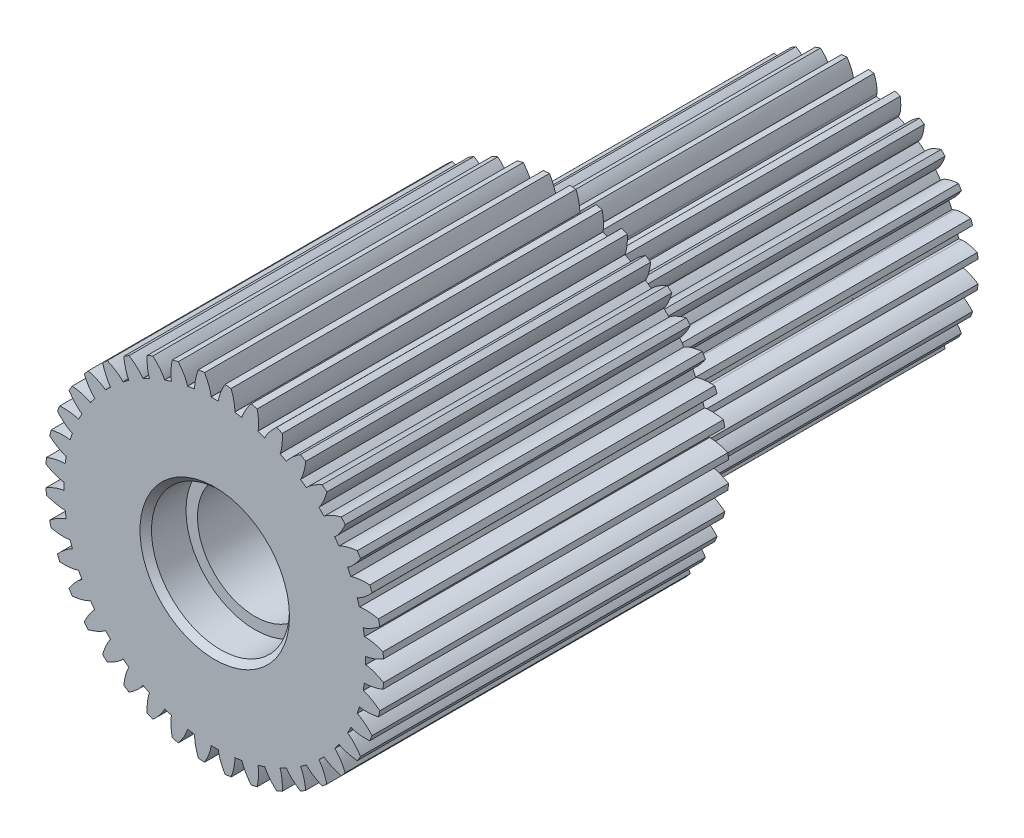
SolidWorks part; units mm, degrees
material "PLA"
ref_plane "Front Plane" through (0, 0, 0) normal (0, 0, 1) x (1, 0, 0)
ref_plane "Top Plane" through (0, 0, 0) normal (0, 1, 0) x (1, 0, 0)
ref_plane "Right Plane" through (0, 0, 0) normal (1, 0, 0) x (0, 0, -1)
sketch "Sketch1" plane through (0, 0, 0) normal (0, 0, 1) x (1, 0, 0)
  circle A0 centre (0, 0) radius 14.7
  dimension "D1" = 29.4
extrude "Boss-Extrude1" add sketch "Sketch1" along normal mid plane 29.9958
sketch "Sketch2" plane through (0, 0, 0) normal (0, 0, 1) x (1, 0, 0)
  line L0 (0, 0) -> (13.9958, 0.3411) construction
  line L1 (0, 0) -> (14, 0) construction
  line L2 (0, 0) -> (13.9958, -0.3411) construction
  line L3 (13.1493, -0.3205) -> (13.1211, -0.3198)
  line L4 (13.1518, 0.3205) -> (13.1211, 0.3198)
  circle A0 centre (0, 0) radius 14 construction
  circle A1 centre (0, 0) radius 13.1557 construction
  circle A2 centre (0, 0) radius 13.125
  circle A3 centre (0, 0) radius 14.7 construction
  circle A4 centre (0, 0) radius 14.7
  spline S0 degree 4 poles (13.1518, 0.3205) (13.1563, 0.3207) (13.1689, 0.3214) (13.1927, 0.3235) (13.2314, 0.328) (13.2806, 0.3354) (13.344, 0.3469) (13.4184, 0.3629) (13.4998, 0.3829) (13.5879, 0.4075) (13.6755, 0.4343) (13.7623, 0.4634) (13.8485, 0.4943) (13.9523, 0.5341) (14.0761, 0.5851) (14.2195, 0.6494) (14.3807, 0.7279) (14.5433, 0.8137) (14.7019, 0.9031) (14.8603, 0.9988) (15.0122, 1.0952) (15.1681, 1.201) (15.3109, 1.3014) (15.4686, 1.4199) (15.5951, 1.5173) (15.7594, 1.6522) (15.8557, 1.7337) (15.9673, 1.8313) (16.0164, 1.8758) (16.0466, 1.9031) knots 0 0 0 0 0 0.005377 0.015084 0.028532 0.04661 0.064855 0.092111 0.119476 0.146842 0.174209 0.201575 0.228941 0.256307 0.307035 0.361767 0.4165 0.471232 0.525964 0.580697 0.635429 0.690161 0.744894 0.799626 0.854358 0.909091 0.954545 1 1 1 1 1 construction
  spline S1 degree 4 poles (13.1518, 0.3205) (13.1563, 0.3207) (13.1689, 0.3214) (13.1927, 0.3235) (13.2314, 0.328) (13.2806, 0.3354) (13.344, 0.3469) (13.4184, 0.3629) (13.4998, 0.3829) (13.5879, 0.4075) (13.6755, 0.4343) (13.7623, 0.4634) (13.8485, 0.4943) (13.9523, 0.5341) (14.0761, 0.5851) (14.2195, 0.6494) (14.3807, 0.7279) (14.5433, 0.8137) (14.7019, 0.9031) (14.8603, 0.9988) (15.0122, 1.0952) (15.1681, 1.201) (15.3109, 1.3014) (15.4686, 1.4199) (15.5951, 1.5173) (15.7238, 1.6229) (15.7861, 1.6751) (15.8178, 1.702) knots 0 0 0 0 0 0.005377 0.015084 0.028532 0.04661 0.064855 0.092111 0.119476 0.146842 0.174209 0.201575 0.228941 0.256307 0.307035 0.361767 0.4165 0.471232 0.525964 0.580697 0.635429 0.690161 0.744894 0.799626 0.854358 0.909091 0.909091 0.909091 0.909091 0.909091
  spline S2 degree 4 poles (13.1493, -0.3205) (13.1538, -0.3206) (13.1664, -0.3213) (13.1902, -0.3234) (13.2289, -0.3279) (13.2781, -0.3354) (13.3415, -0.3469) (13.4159, -0.3628) (13.4973, -0.3829) (13.5855, -0.4074) (13.673, -0.4343) (13.7599, -0.4633) (13.846, -0.4942) (13.9498, -0.534) (14.0736, -0.585) (14.2171, -0.6493) (14.3783, -0.7278) (14.5409, -0.8137) (14.6994, -0.903) (14.8578, -0.9987) (15.0098, -1.0952) (15.1656, -1.2009) (15.3085, -1.3013) (15.4661, -1.4198) (15.5927, -1.5173) (15.757, -1.6521) (15.8532, -1.7337) (15.9649, -1.8312) (16.0139, -1.8757) (16.0442, -1.9031) knots 0 0 0 0 0 0.005377 0.015084 0.028532 0.04661 0.064855 0.092111 0.119476 0.146842 0.174209 0.201575 0.228941 0.256307 0.307035 0.361767 0.4165 0.471232 0.525964 0.580697 0.635429 0.690161 0.744894 0.799626 0.854358 0.909091 0.954545 1 1 1 1 1 construction
  spline S3 degree 4 poles (13.1493, -0.3205) (13.1538, -0.3206) (13.1664, -0.3213) (13.1902, -0.3234) (13.2289, -0.3279) (13.2781, -0.3354) (13.3415, -0.3469) (13.4159, -0.3628) (13.4973, -0.3829) (13.5855, -0.4074) (13.673, -0.4343) (13.7599, -0.4633) (13.846, -0.4942) (13.9498, -0.534) (14.0736, -0.585) (14.2171, -0.6493) (14.3783, -0.7278) (14.5409, -0.8137) (14.6994, -0.903) (14.8578, -0.9987) (15.0098, -1.0952) (15.1656, -1.2009) (15.3085, -1.3013) (15.4661, -1.4198) (15.5927, -1.5173) (15.7214, -1.6229) (15.7837, -1.675) (15.8154, -1.702) knots 0 0 0 0 0 0.005377 0.015084 0.028532 0.04661 0.064855 0.092111 0.119476 0.146842 0.174209 0.201575 0.228941 0.256307 0.307035 0.361767 0.4165 0.471232 0.525964 0.580697 0.635429 0.690161 0.744894 0.799626 0.854358 0.909091 0.909091 0.909091 0.909091 0.909091
  dimension "D1" = 28
  dimension "D2" = 26.3114
  dimension "D3" = 26.25
  dimension "D4" = 1.396
  dimension "D5" = 1.396
extrude "Cut-Extrude1" cut sketch "Sketch2" against normal through all both and the other way through all contours A2 A4 region at (14.0491, -0.0005, 0)
pattern_circular "CirPattern2" count 40 over 360 about axis through (0, 0, 14.9979) along (0, 0, -1) of "Cut-Extrude1"
sketch "Sketch3" plane through (0, 0, 14.9979) normal (0, 0, 1) x (1, 0, 0)
  circle A0 centre (0, 0) radius 5
  dimension "D1" = 10
sketch "Sketch4" plane through (0, 0, -14.9979) normal (0, 0, -1) x (-1, 0, 0)
  circle A0 centre (0, 0) radius 10.5
  dimension "D1" = 21
extrude "Boss-Extrude2" add sketch "Sketch4" along normal blind 25.9129
sketch "Sketch5" plane through (0, 0, -40.9108) normal (0, 0, -1) x (-1, 0, 0)
  line L0 (0, 0) -> (10.5, 0) construction
  line L1 (0, 0) -> (10.4911, 0.4324) construction
  line L2 (0, 0) -> (10.4911, -0.4324) construction
  line L3 (9.1796, 0.3784) -> (8.9174, 0.3676)
  line L4 (9.1796, -0.3784) -> (8.9174, -0.3676)
  circle A0 centre (0, 0) radius 9.209 construction
  circle A1 centre (0, 0) radius 8.925
  arc A2 (10.4584, -0.9339) -> (10.4584, 0.9339) centre (0, 0) ccw
  spline S0 degree 4 poles (9.1796, 0.3784) (9.1827, 0.3785) (9.1915, 0.3792) (9.2082, 0.3809) (9.2352, 0.3846) (9.2853, 0.393) (9.3451, 0.4059) (9.4122, 0.4231) (9.4838, 0.4444) (9.5448, 0.4642) (9.6052, 0.4855) (9.6651, 0.5082) (9.7373, 0.5373) (9.8234, 0.5744) (9.923, 0.6211) (10.0349, 0.678) (10.1477, 0.74) (10.2576, 0.8044) (10.3674, 0.8732) (10.4726, 0.9425) (10.5804, 1.0183) (10.6792, 1.0903) (10.7882, 1.1751) (10.8756, 1.2448) (10.989, 1.3411) (11.0554, 1.3993) (11.1324, 1.4689) (11.1662, 1.5006) (11.187, 1.5201) knots 0 0 0 0 0 0.005377 0.015084 0.028532 0.04661 0.092111 0.119476 0.146842 0.174209 0.201575 0.228941 0.256307 0.307035 0.361767 0.4165 0.471232 0.525964 0.580697 0.635429 0.690161 0.744894 0.799626 0.854358 0.909091 0.954545 1 1 1 1 1 construction
  spline S1 degree 4 poles (9.1796, 0.3784) (9.1827, 0.3785) (9.1915, 0.3792) (9.2082, 0.3809) (9.2352, 0.3846) (9.2853, 0.393) (9.3451, 0.4059) (9.4122, 0.4231) (9.4838, 0.4444) (9.5448, 0.4642) (9.6052, 0.4855) (9.6651, 0.5082) (9.7373, 0.5373) (9.8234, 0.5744) (9.923, 0.6211) (10.0349, 0.678) (10.1477, 0.74) (10.2576, 0.8044) (10.3674, 0.8732) (10.4726, 0.9425) (10.5804, 1.0183) (10.6792, 1.0903) (10.7882, 1.1751) (10.8756, 1.2448) (10.9644, 1.3202) (11.0074, 1.3575) (11.0293, 1.3767) knots 0 0 0 0 0 0.005377 0.015084 0.028532 0.04661 0.092111 0.119476 0.146842 0.174209 0.201575 0.228941 0.256307 0.307035 0.361767 0.4165 0.471232 0.525964 0.580697 0.635429 0.690161 0.744894 0.799626 0.854358 0.909091 0.909091 0.909091 0.909091 0.909091
  spline S2 degree 4 poles (9.1796, -0.3784) (9.1827, -0.3785) (9.1915, -0.3792) (9.2082, -0.3809) (9.2352, -0.3846) (9.2853, -0.393) (9.3451, -0.4059) (9.4122, -0.4231) (9.4838, -0.4444) (9.5448, -0.4642) (9.6052, -0.4855) (9.6651, -0.5082) (9.7373, -0.5373) (9.8234, -0.5744) (9.923, -0.6211) (10.0349, -0.678) (10.1477, -0.74) (10.2576, -0.8044) (10.3674, -0.8732) (10.4726, -0.9425) (10.5804, -1.0183) (10.6792, -1.0903) (10.7882, -1.1751) (10.8756, -1.2448) (10.989, -1.3411) (11.0554, -1.3993) (11.1324, -1.4689) (11.1662, -1.5006) (11.187, -1.5201) knots 0 0 0 0 0 0.005377 0.015084 0.028532 0.04661 0.092111 0.119476 0.146842 0.174209 0.201575 0.228941 0.256307 0.307035 0.361767 0.4165 0.471232 0.525964 0.580697 0.635429 0.690161 0.744894 0.799626 0.854358 0.909091 0.954545 1 1 1 1 1 construction
  spline S3 degree 4 poles (9.1796, -0.3784) (9.1827, -0.3785) (9.1915, -0.3792) (9.2082, -0.3809) (9.2352, -0.3846) (9.2853, -0.393) (9.3451, -0.4059) (9.4122, -0.4231) (9.4838, -0.4444) (9.5448, -0.4642) (9.6052, -0.4855) (9.6651, -0.5082) (9.7373, -0.5373) (9.8234, -0.5744) (9.923, -0.6211) (10.0349, -0.678) (10.1477, -0.74) (10.2576, -0.8044) (10.3674, -0.8732) (10.4726, -0.9425) (10.5804, -1.0183) (10.6792, -1.0903) (10.7882, -1.1751) (10.8756, -1.2448) (10.9644, -1.3202) (11.0074, -1.3575) (11.0293, -1.3767) knots 0 0 0 0 0 0.005377 0.015084 0.028532 0.04661 0.092111 0.119476 0.146842 0.174209 0.201575 0.228941 0.256307 0.307035 0.361767 0.4165 0.471232 0.525964 0.580697 0.635429 0.690161 0.744894 0.799626 0.854358 0.909091 0.909091 0.909091 0.909091 0.909091
  dimension "D2" = 17.85
  dimension "D3" = 21
  dimension "D1" = 18.418
  dimension "D4" = 2.36
  dimension "D5" = 2.36
extrude "Cut-Extrude2" cut sketch "Sketch5" against normal up to surface (25.9129 mm away) contours A2 A1 region at (-9.842, 0, -40.9108) up to face at (10.5, 0, -14.9979)
pattern_circular "CirPattern3" count 28 over 360 about axis through (0, 0, -40.9108) along (0, 0, 1) of "Cut-Extrude2"
extrude "Cut-Extrude3" cut sketch "Sketch3" against normal through all contours A0
sketch "Sketch7" plane through (0, 0, -40.9108) normal (0, 0, -1) x (-1, 0, 0)
  circle A0 centre (0, 0) radius 6
  dimension "D1" = 12
extrude "Cut-Extrude4" cut sketch "Sketch7" against normal blind 3.5
ref_plane "Plane1" through (0, 0, -12.9565) normal (0, 0, -1) x (-1, 0, 0)
mirror "Mirror1" about plane through (0, 0, -12.9565) normal (0, 0, -1) of "Cut-Extrude4"
chamfer "Chamfer1" distance 0.5 angle 45 2 edges at (-6, 0, 14.9979) (-6, 0, -40.9108)
equation "\"module\" = 0.7"
equation "\"pressure angle\" = 20.0"
equation "\"h_a\" = 0.7"
equation "\"h_b\" = 0.875"
equation "\"clr_tip_root\" = 0.17500000000000004"
equation "\"D1@Sketch1\" = \"dp_p_b\" + 2 * \"h_a\""
equation "\"D1@Boss-Extrude1\" = \"fw_p_b\""
equation "\"D1@Sketch2\" = \"dp_p_b\""
equation "\"D2@Sketch2\"= \"db_p_b\""
equation "\"D3@Sketch2\" = \"dp_p_b\" - 2 * \"h_b\""
equation "\"Nr_s\" = 116"
equation "\"pressure_angle\" = 20.0"
equation "\"h_f\" = 0.875"
equation "\"dp_r_s\" = 81.19999999999999"
equation "\"bearing_ID\" = 70"
equation "\"bearing_OD\" = 90"
equation "\"bearing_height\" = 10"
equation "\"clearance_planet\" = 1.5"
equation "\"case_dist\" = 6.5"
equation "\"Motor_case_OD_max\" = 131.3"
equation "\"case_mounting_PCD\" = 123.8"
equation "\"bearing mount thickness\" = 8"
equation "\"case_mounting_hole_dia\" = 3"
equation "\"output_mounting_PCD\" = 98"
equation "\"output_mounting_hole_dia\" = 4"
equation "\"clearance_case_mount_holes_shell_thickness\" = 1"
equation "\"motor_case_OD_base\" = 121.8"
equation "\"sec_carrier_thickness\" = 5"
equation "\"sun_coupler_hub_thickness\" = 4"
equation "\"clearance_sun_coupler_sec_carrier\" = 1.5"
equation "\"clearance_motor_and_case\" = 5"
equation "\"motor_OD\" = 106.8"
equation "\"Motor_case_thickness\" = 2.5"
equation "\"Motor_case_ID\" = 116.8"
equation "\"case_mounting_hole_shift\" = 1.0"
equation "\"output_mounting_nut_wrench_size\" = 7"
equation "\"output_mounting_nut_thickness\" = 3.2"
equation "\"case_mounting_hole_allen_socket_dia\" = 5.5"
equation "\"output_mounting_nut_depth\" = 3"
equation "\"case_mounting_bolt_depth\" = 4.5"
equation "\"Ns\" = 48"
equation "\"ring_radial_thickness\" = 5"
equation "\"ring_to_chamfer_clearance\" = 1.5"
equation "\"Motor_case_OD_base_to_chamfer\" = 5"
equation "\"pattern_offset_from_motor_case_OD_base\" = 3"
equation "\"pattern_bulge_dia\" = 3"
equation "\"pattern_num_bulge\" = 18"
equation "\"pattern_depth\" = 2"
equation "\"motor_height\" = 47.6"
equation "\"case_mounting_wrench_size\" = 5.5"
equation "\"case_mounting_nut_clearance\" = 2"
equation "\"base_plate_thickness\" = 4"
equation "\"case_mounting_nut_thickness\" = 2.4"
equation "\"case_mounting_surface_height\" = 4"
equation "\"motor_mount_hole_PCD\" = 40"
equation "\"motor_mount_hole_dia\" = 5"
equation "\"motor_mount_hole_num\" = 4"
equation "\"central_hole_offset_from_motor_mount_PCD\" = 5"
equation "\"wire_slot_dist_from_center\" = 45.5"
equation "\"wire_slot_length\" = 10"
equation "\"wire_slot_radius\" = 3"
equation "\"driver_upper_holes_dist_from_center\" = 29"
equation "\"driver_lower_holes_dist_from_center\" = 13"
equation "\"driver_side_holes_dist_from_center\" = 22.5"
equation "\"driver_mount_holes_dia\" = 3"
equation "\"driver_mount_inserts_OD\" = 4.8"
equation "\"driver_mount_thickness\" = 1.5"
equation "\"driver_mount_height\" = 6"
equation "\"air_flow_hole_offset\" = 3"
equation "\"num_planet\" = 4"
equation "\"planet_pin_bolt_dia\" = 5"
equation "\"planet_pin_socket_head_dia\" = 8.5"
equation "\"carrier_PCD\" = 61.599999999999994"
equation "\"planet_shaft_dia\" = 8"
equation "\"planet_shaft_step_offset\" = 1"
equation "\"carrier_trapezoidal_support_sun_offset\" = 5"
equation "\"carrier_trapezoidal_support_hole_PCD_offset_bearing_ID\" = 4"
equation "\"carrier_trapezoidal_support_hole_dia\" = 3"
equation "\"carrier_trapezoidal_support_hole_socket_head_dia\" = 5.5"
equation "\"carrier_bearing_step_width\" = 1.5"
equation "\"standard_clearance_1_5mm\" = 1.5"
equation "\"standard_fillet_1_5mm\" = 1.5"
equation "\"sun_shaft_bearing_OD\" = 16"
equation "\"sun_shaft_bearing_width\" = 5"
equation "\"standard_bearing_insertion_chamfer\" = 0.5"
equation "\"carrier_trapezoidal_support_hole_wrench_size\" = 5.5"
equation "\"planet_pin_bolt_wrench_size\" = 8"
equation "\"planet_bearing_OD\" = 12"
equation "\"planet_bearing_width\" = 3.5"
equation "\"planet_bore\" = 10"
equation "\"D1@Sketch3\"=\"planet_bore\""
equation "\"Np_b\" = 40"
equation "\"dp_s\" = 33.599999999999994"
equation "\"db_s\" = 31.57367205840652"
equation "\"fw_s_calc\" = 5.685933367726717"
equation "\"alpha_s\" = 0.8539582918412343"
equation "\"beta_s\" = 2.0420834163175314"
equation "\"dp_p_b\" = 28.0"
equation "\"db_p_b\" = 26.311393382005434"
equation "\"fw_p_s\" = 25.912913082891553"
equation "\"alpha_p_b\" = 0.8539582918412485"
equation "\"beta_p_b\" = 2.792083416317503"
equation "\"motor_output_hole_PCD\" = 23"
equation "\"motor_output_hole_dia\" = 4"
equation "\"motor_output_hole_num\" = 4"
equation "\"sun_shaft_bearing_ID\" = 8"
equation "\"sun_hub_dia\" = 30.0"
equation "\"sun_central_bolt_dia\" = 5"
equation "\"sun_central_bolt_socket_head_dia\" = 8.5"
equation "\"fw_s_used\" = 63.40868620995457"
equation "\"motor_output_hole_CSK_OD\" = 8"
equation "\"motor_output_hole_CSK_head_height\" = 2.0"
equation "\"bearing_retainer_thickness\" = 2"
equation "\"Np_s\" = 28"
equation "\"fw_p_b\" = 29.99577312706301"
equation "\"dp_p_s\" = 19.599999999999998"
equation "\"db_p_s\" = 18.417975367403802"
equation "\"alpha_p_s\" = 0.8539582918412592"
equation "\"beta_p_s\" = 4.7206548448889105"
equation "\"D1@Sketch4\"=\"dp_p_s\" + 2 * \"h_a\""
equation "\"D1@Boss-Extrude2\"=\"fw_p_s\""
equation "\"D2@Sketch5\"=\"dp_p_s\" - 2 * \"h_b\""
equation "\"D3@Sketch5\"=\"dp_p_s\"+2 * \"h_a\" "
equation "\"D1@Sketch5\"=\"db_p_s\""
equation "\"D1@CirPattern3\"=\"Np_s\""
equation "\"D4@Sketch5\"=\"beta_p_s\"/2"
equation "\"D5@Sketch5\"=\"beta_p_s\"/2"
equation "\"D4@Sketch2\"=\"beta_p_b\"/2"
equation "\"D5@Sketch2\"=\"beta_p_b\"/2"
equation "\"D1@Sketch7\"=\"planet_bearing_OD\""
equation "\"D1@Cut-Extrude4\"=\"planet_bearing_width\""
equation "\"D1@Chamfer1\"=\"standard_bearing_insertion_chamfer\""
equation "\"D1@CirPattern2\"=\"Np_b\""
equation "\"Nr_b\" = 128"
equation "\"dp_r_b\" = 89.6"
equation "\"db_r_b\" = 84.19645882241738"
equation "\"fw_r_b\" = 29.99577312706301"
equation "\"alpha_r_b\" = 0.8539582918412556"
equation "\"beta_r_b\" = 3.114166583682511"
equation "\"ring_OD_b\" = 99.6"
equation "\"Fillet10\"= IIF ( \"ring_OD_b\" > ( \"bearing_OD\" + 2 * \"bearing mount thickness\" ) , \"suppressed\" , \"unsuppressed\" )"
equation "\"Fillet11\"= IIF ( \"ring_OD_b\" < ( \"bearing_OD\" + 2 * \"bearing mount thickness\" ) , \"suppressed\" , \"unsuppressed\" )"
equation "\"clr_tip_root_s\" = 0.17500000000000004"
equation "\"db_r_s\" = 76.30304080781575"
equation "\"fw_r_s\" = 24.412913082891553"
equation "\"alpha_r_s\" = 0.8539582918412556"
equation "\"beta_r_s\" = 3.259640721613546"
equation "\"small_ring_case_thickness\" = 4"
equation "\"carrier_thickness\" = 4"
equation "\"small_ring_output_wall_thickness\" = 5"
equation "\"small_ring_output_wall_to_bearing_shaft_attachement_hole_dia\" = 4"
equation "\"small_ring_output_wall_to_bearing_shaft_attachement_hole_depth\" = 6.5"
equation "\"small_ring_output_wall_to_bearing_shaft_attachement_nut_wrench\" = 7"
equation "\"small_ring_output_wall_to_bearing_shaft_attachement_nut_thickness\" = 3.2"
equation "\"small_ring_output_wall_to_bearing_shaft_attachement_hole_pcd\" = 12"
equation "\"small_ring_output_wall_to_bearing_shaft_attachement_hole_num\" = 3"
equation "\"small_ring_output_wall_to_bearing_shaft_attachement_hole_CSK_OD\" = 8"
equation "\"small_ring_output_wall_to_bearing_shaft_attachement_hole_CSK_head_height\" = 2.0"
equation "\"carrier_small_ring_inner_bearing_ID\" = 20"
equation "\"carrier_small_ring_inner_bearing_OD\" = 32"
equation "\"carrier_small_ring_inner_bearing_height\" = 7"
equation "\"carrier_small_ring_inner_bearing_flap\" = 2"
equation "\"gear_casing_big_ring_to_bearing_dist\" = 34.91291308289155"
equation "\"gear_casing_thickness\" = 4"
